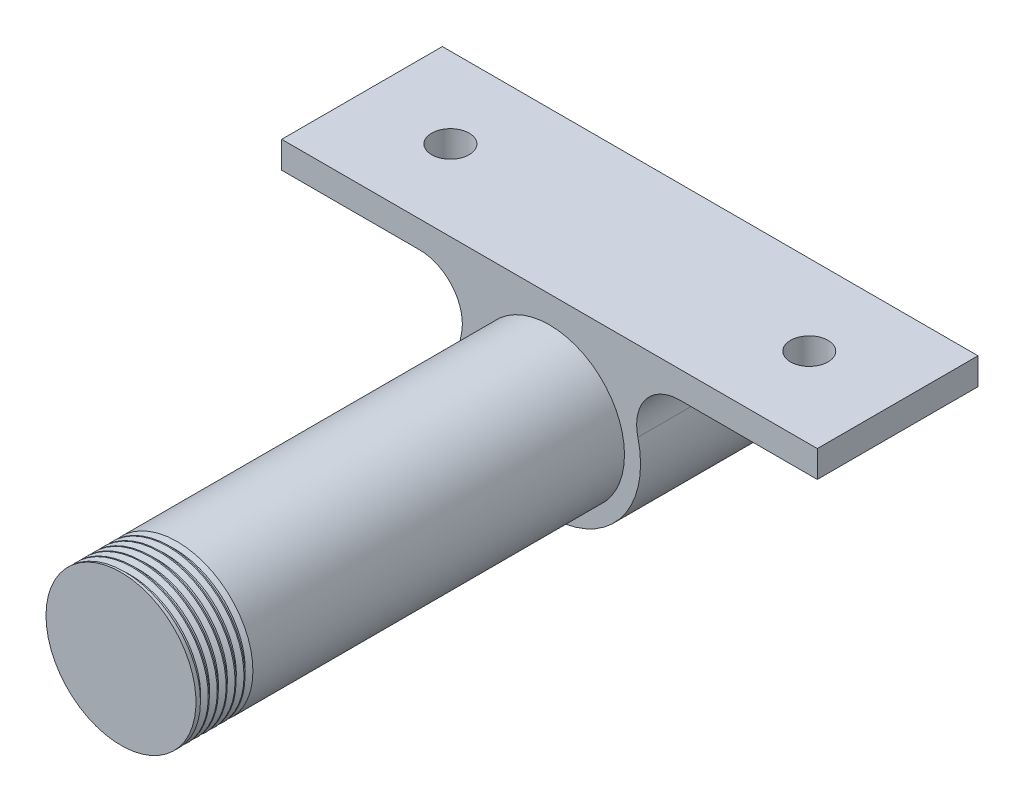
SolidWorks part; units mm, degrees
ref_plane "Front Plane" through (0, 0, 0) normal (0, 0, 1) x (1, 0, 0)
ref_plane "Top Plane" through (0, 0, 0) normal (0, 1, 0) x (1, 0, 0)
ref_plane "Right Plane" through (0, 0, 0) normal (1, 0, 0) x (0, 0, -1)
sketch "Sketch6" plane through (0, 0, 0) normal (0, 0, 1) x (1, 0, 0)
  circle A0 centre (0, 0) radius 8.89
  circle A1 centre (0, 0) radius 10.795
  dimension "D1" = 17.78
  dimension "D2" = 21.59
extrude "Boss-Extrude3" add sketch "Sketch6" along normal blind 19.05
ref_plane "Plane3" through (0, 10.795, 0) normal (0, 1, 0) x (1, 0, 0)
sketch "Sketch7" plane through (0, 10.795, 0) normal (0, 1, 0) x (1, 0, 0)
  line L0 (-31.75, 0) -> (31.75, 0)
  line L1 (0, 0) -> (0, -19.05) construction
  line L2 (-10.795, -19.05) -> (10.795, -19.05) construction
  line L3 (-10.795, -19.05) -> (-31.75, -19.05)
  line L4 (-31.75, -19.05) -> (-31.75, 0)
  line L5 (-10.795, -19.05) -> (31.75, -19.05)
  line L6 (31.75, -19.05) -> (31.75, 0)
  line L7 (-10.795, 0) -> (-10.795, -19.05)
  line L8 (10.795, 0) -> (10.795, -19.05)
  line L9 (10.795, -19.05) -> (10.795, 0) construction
  line L10 (-31.75, 0) -> (-10.795, -19.05) construction
  line L11 (-10.795, 0) -> (-31.75, -19.05) construction
  line L12 (10.795, 0) -> (31.75, -19.05) construction
  line L13 (31.75, 0) -> (10.795, -19.05) construction
  circle A0 centre (-21.2725, -9.525) radius 2.2225
  circle A1 centre (21.2725, -9.525) radius 2.2225
  dimension "D2" = 4.445
  dimension "D3" = 4.445
  dimension "D1" = 63.5
extrude "Boss-Extrude4" add sketch "Sketch7" against normal blind 1.905 and the other way blind 1.27 contours L0 L8 L5 L6 A1 | L7 L0 L4 L3 A0 | L8 L0 L7 L5 region at (-21.2725, 10.795, 0.2832) region at (0, 10.795, 9.525) region at (21.2725, 10.795, 0.2832)
fillet "Fillet1" radius 5.08 2 edges at (-6.1237, 8.89, 9.525) (6.1237, 8.89, 9.525)
sketch "Sketch8" plane through (0, 0, 0) normal (0, 0, 1) x (1, 0, 0)
  circle A0 centre (0, 0) radius 8.89
  dimension "D1" = 17.78
extrude "Boss-Extrude5" add sketch "Sketch8" along normal blind 69.85
thread "Thread1" pitch 1.0583 method cut profile "Thread Profile2" start angle 0, offset 0, length 6.35, pitch 1.0583, diameter 17.78
ref_plane "Plane5" through (-8.89, 0, 69.85) normal (0, -1, 0) x (-1, 0, 0)
sketch "Thread Profile2" plane through (-8.89, 0, 69.85) normal (0, -1, 0) x (-1, 0, 0)
  line L0 (0, 0) -> (0, 1.0583) construction
  line L11 (0, 0) -> (0, 0.926)
  line L12 (0, 0.926) -> (-0.5728, 0.5953)
  line L13 (-0.5728, 0.5953) -> (-0.5728, 0.3307)
  line L15 (-0.5728, 0.3307) -> (0, 0)
  line L17 (-0.5728, 0.463) -> (0, 0.463) construction
  point P2 (0, 0)
  dimension "Pitch" = 1.0583
  dimension "Profile_Angle" = 60
  dimension "Profile_Land" = 0.2646
  dimension "Profile_Height" = 0.5728
